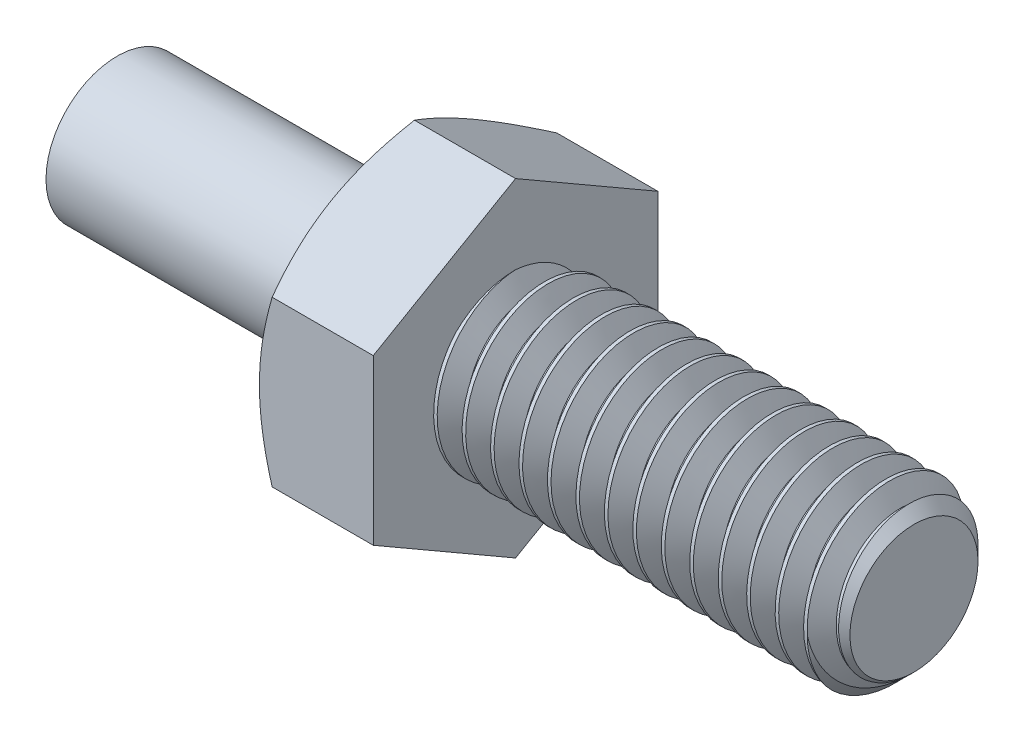
SolidWorks part; units mm, degrees
ref_plane "Front Plane" through (0, 0, 0) normal (0, 0, 1) x (1, 0, 0)
ref_plane "Top Plane" through (0, 0, 0) normal (0, 1, 0) x (1, 0, 0)
ref_plane "Right Plane" through (0, 0, 0) normal (1, 0, 0) x (0, 0, -1)
sketch "Sketch1" plane through (0, 0, 0) normal (0, 0, 1) x (1, 0, 0)
  line L0 (-9, 0) -> (9, 0) construction
  line L1 (-5, 5) -> (-5, -5) construction
  line L2 (-9, 5) -> (-9, -5) construction
  line L3 (9, 3) -> (9, -3) construction
  point P8 (5.5, -3)
  dimension "Thread Dia" = 6
  dimension "Hex" = 10
  dimension "Head Ht" = 4
  dimension "Length" = 14
  dimension "D1" = 3.5
ref_plane "Plane2" through (9, 0, 0) normal (1, 0, 0) x (0, 0, -1)
sketch "Sketch2" plane through (9, 0, 0) normal (1, 0, 0) x (0, 0, -1)
  circle A0 centre (0, 0) radius 3
extrude "Boss-Extrude1" add sketch "Sketch2" against normal up to vertex (14 mm away) up to point (-5, -5, 0)
sketch "Sketch4" plane through (9, 0, 0) normal (1, 0, 0) x (0, 0, -1)
  circle A1 centre (0, 0) radius 3
  circle A2 centre (0, 0) radius 3
  dimension "D1" = 0
curve "Helix/Spiral1" pitch 1 height 15 turns 15 parameters "Pitch"=1
chamfer "Chamfer1" distance 0.75 angle 45 1 edges at (9, 0, -3)
sketch "Sketch5" plane through (0, 0, 0) normal (0, 0, 1) x (1, 0, 0)
  line L0 (9, 3) -> (9.375, 2.3505)
  line L1 (9.375, 2.3505) -> (9.5, 2.3505)
  line L2 (9.5, 2.3505) -> (9.875, 3)
  line L3 (9, 3) -> (9.875, 3)
  line L4 (9.4375, 2.3505) -> (9.4375, 3) construction
  line L5 (9.1875, 2.6752) -> (9.6875, 2.6752) construction
  line L6 (9, -3) -> (9, 3) construction
  dimension "D1" = 60
  dimension "D2" = 0.125
  dimension "D3" = 0.5
sweep "Cut-Sweep1" cut profiles "Sketch5" path "Helix/Spiral1"
sketch "Sketch3" plane through (-5, 0, 0) normal (-1, 0, 0) x (0, 0, 1)
  line L0 (0, 5) -> (0, -5) construction
  line L1 (-5, -2.8868) -> (0, -5.7735)
  line L2 (0, -5.7735) -> (5, -2.8868)
  line L3 (5, -2.8868) -> (5, 2.8868)
  line L4 (5, 2.8868) -> (0, 5.7735)
  line L5 (0, 5.7735) -> (-5, 2.8868)
  line L6 (-5, 2.8868) -> (-5, -2.8868)
  circle A0 centre (0, 0) radius 5 construction
extrude "Boss-Extrude2" add sketch "Sketch3" along normal up to vertex (4 mm away) up to point (-9, -5, 0)
sketch "Sketch6" plane through (-9, 0, 0) normal (-1, 0, 0) x (0, 0, 1)
  circle A0 centre (0, 0) radius 5 construction
  circle A1 centre (0, 0) radius 5
extrude "Cut-Extrude1" cut sketch "Sketch6" against normal through all draft 60 flip side to cut
sketch "Sketch9" plane through (0, 0, 0) normal (0, 0, 1) x (1, 0, 0)
  line L0 (-5, 3) -> (-5, 0)
  line L1 (-5, 0) -> (-42, 0)
  line L2 (-42, 0) -> (-45, 3)
  line L3 (-45, 3) -> (-5, 3)
  line L4 (-9, 0) -> (9, 0) construction
  line L5 (-5, 5) -> (-5, -5) construction
  line L6 (9, 3) -> (9, -3) construction
  dimension "D1" = 45
  dimension "MinThreadLg" = 54
revolve "Revolve1" [suppressed] add sketch "Sketch9" angle 360 about L1
sketch "Sketch10" plane through (-9, 0, 0) normal (-1, 0, 0) x (0, 0, 1)
  circle A0 centre (0, 0) radius 2.5
  dimension "D1" = 5
extrude "Boss-Extrude3" add sketch "Sketch10" along normal blind 10
equation "\"D2@Sketch5\" = \"Pitch@Helix/Spiral1\"*.125"
equation "\"D3@Sketch5\" = \"Pitch@Helix/Spiral1\"*.50"
equation "\"D3@Helix/Spiral1\" = \"Length@Sketch1\"+\"Pitch@Helix/Spiral1\""
equation "\"D1@Chamfer1\" = \"Pitch@Helix/Spiral1\"*.750"
equation "\"D1@Sketch1\" = \"Pitch@Helix/Spiral1\"*3.50"
